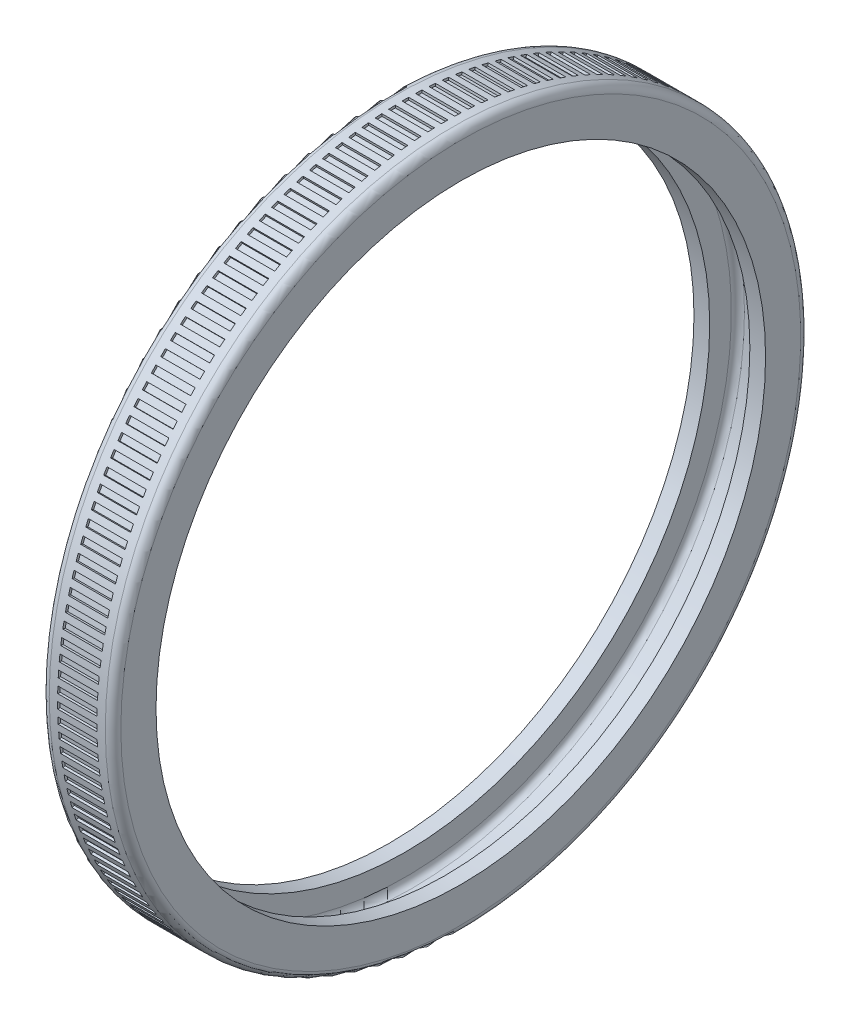
SolidWorks part; units mm, degrees
material "Rubber"
ref_plane "Front" through (0, 0, 0) normal (0, 0, 1) x (1, 0, 0)
ref_plane "Top" through (0, 0, 0) normal (0, 1, 0) x (1, 0, 0)
ref_plane "Right" through (0, 0, 0) normal (1, 0, 0) x (0, 0, -1)
sketch "Sketch1" plane through (0, 0, 0) normal (0, 0, 1) x (1, 0, 0)
  line L0 (-1000, 0) -> (49000, 0) construction
  line L1 (-4.375, 37.25) -> (-4.375, 41.55)
  line L2 (-3.425, 42.5) -> (3.425, 42.5)
  line L3 (4.375, 41.55) -> (4.375, 37.25)
  line L4 (4.375, 37.25) -> (2.4543, 37.25)
  line L5 (-4.375, 37.25) -> (-2.4543, 37.25)
  line L6 (-2.4543, 37.25) -> (-2.4543, 39.9)
  line L7 (-1.6543, 40.7) -> (1.6543, 40.7)
  line L8 (2.4543, 39.9) -> (2.4543, 37.25)
  arc A0 (-4.375, 41.55) -> (-3.425, 42.5) centre (-3.425, 41.55) cw
  arc A1 (3.425, 42.5) -> (4.375, 41.55) centre (3.425, 41.55) cw
  arc A2 (-2.4543, 39.9) -> (-1.6543, 40.7) centre (-1.6543, 39.9) cw
  arc A3 (1.6543, 40.7) -> (2.4543, 39.9) centre (1.6543, 39.9) cw
  point P10 (0, 42.5)
  dimension "D3" = 0.95
  dimension "D6" = 0.8
  dimension "D1" = 85
  dimension "D2" = 8.75
  dimension "D4" = 5.25
  dimension "D5" = 4.9087
  dimension "D7" = 1.8
revolve "Revolve1" add sketch "Sketch1" angle 360 about L0
sketch "Sketch2" plane through (0, 0, 0) normal (1, 0, 0) x (0, 0, -1)
  line L1 (-0.4, 44.2) -> (0.4, 44.2)
  line L2 (-0.4, 44.2) -> (-0.4, 42.2)
  line L3 (-0.4, 42.2) -> (0.4, 42.2)
  line L4 (0.4, 44.2) -> (0.4, 42.2)
  line L5 (-0.4, 44.2) -> (0.4, 42.2) construction
  line L6 (-0.4, 42.2) -> (0.4, 44.2) construction
  circle A0 centre (0, 0) radius 42.5 construction
  point P0 (0, 43.2)
  point P5 (0, 42.5)
  dimension "D1" = 0.3
  dimension "D2" = 0.8
  dimension "D3" = 2
extrude "Cut-Extrude1" cut sketch "Sketch2" against normal mid plane 4.8
pattern_circular "CirPattern1" count 163 over 360 about axis through (-1000, 0, 0) along (-1, 0, 0) of "Cut-Extrude1"
